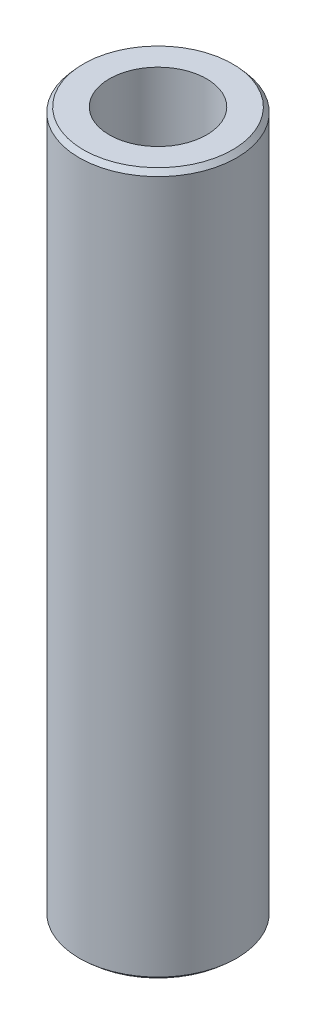
SolidWorks part; units mm, degrees
ref_plane "Front Plane" through (0, 0, 0) normal (0, 0, 1) x (1, 0, 0)
ref_plane "Top Plane" through (0, 0, 0) normal (0, 1, 0) x (1, 0, 0)
ref_plane "Right Plane" through (0, 0, 0) normal (1, 0, 0) x (0, 0, -1)
sketch "Sketch1" plane through (0, 0, 0) normal (0, 1, 0) x (1, 0, 0)
  circle A0 centre (0, 0) radius 15
  dimension "SHAFT_OD" = 30
extrude "Boss-Extrude1" add sketch "Sketch1" along normal blind 133.7828
sketch "Sketch2" plane through (0, 0, 0) normal (0, 1, 0) x (1, 0, 0)
  circle A0 centre (0, 0) radius 9.2668
  dimension "BORE_D" = 18.5335
extrude "Cut-Extrude1" cut sketch "Sketch2" along normal through all
chamfer "Chamfer1" distance 0.9135 angle 41.24 2 edges at (0, 133.7828, 15) (0, 0, 15) first distance on face at (0, 133.7828, 15) first distance on face at (0, 0, 9.2668)
